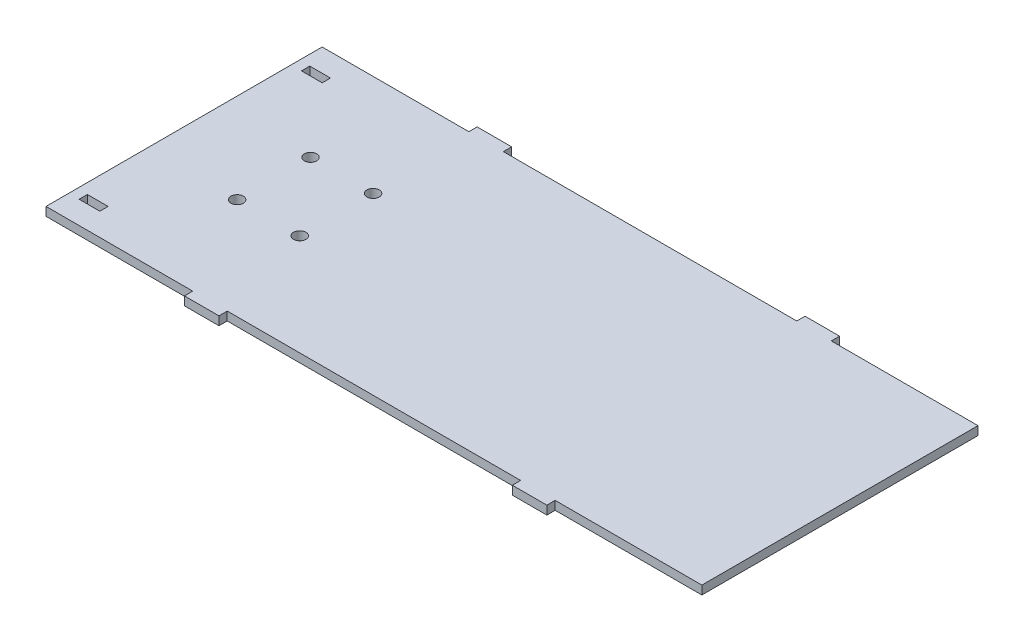
SolidWorks part; units mm, degrees
ref_plane "Front Plane" through (0, 0, 0) normal (0, 0, 1) x (1, 0, 0)
ref_plane "Top Plane" through (0, 0, 0) normal (0, 1, 0) x (1, 0, 0)
ref_plane "Right Plane" through (0, 0, 0) normal (1, 0, 0) x (0, 0, -1)
sketch "Sketch1" plane through (0, 0, 0) normal (0, 1, 0) x (1, 0, 0)
  line L0 (-12.7, 76.2164) -> (228.6, 76.2164) construction
  line L1 (0, 0) -> (41.275, 0)
  line L3 (0, 101.6) -> (41.275, 101.6)
  line L4 (228.6, 0) -> (228.6, 101.6)
  line L9 (0, 0) -> (-12.7, 0)
  line L11 (0, 101.6) -> (-12.7, 101.6)
  line L12 (-12.7, 0) -> (-12.7, 101.6)
  line L13 (107.95, 50.8) -> (228.6, 50.8) construction
  line L14 (174.625, 101.6) -> (228.6, 101.6)
  line L16 (161.925, 101.6) -> (161.925, 104.648)
  line L17 (161.925, 104.648) -> (174.625, 104.648)
  line L18 (174.625, 101.6) -> (174.625, 104.648)
  line L19 (107.95, 76.2164) -> (107.95, 0) construction
  line L20 (174.625, 0) -> (174.625, -3.048)
  line L21 (161.925, 0) -> (161.925, -3.048)
  line L22 (161.925, -3.048) -> (174.625, -3.048)
  line L23 (41.275, 0) -> (41.275, -3.048)
  line L24 (53.975, 0) -> (53.975, -3.048)
  line L25 (53.975, -3.048) -> (41.275, -3.048)
  line L26 (41.275, 101.6) -> (41.275, 104.648)
  line L27 (53.975, 101.6) -> (53.975, 104.648)
  line L28 (53.975, 104.648) -> (41.275, 104.648)
  line L29 (174.625, 0) -> (228.6, 0)
  line L30 (53.975, 101.6) -> (161.925, 101.6)
  line L31 (53.975, 0) -> (161.925, 0)
  point P15 (168.275, 104.648)
  point P16 (168.275, 50.8)
  dimension "D1" = 228.6
  dimension "D2" = 101.6
  dimension "D3" = 3.048
  dimension "D4" = 12.7
extrude "Main Frame" add sketch "Sketch1" along normal blind 3.175
sketch "Sketch2" plane through (0, 3.175, 0) normal (0, 1, 0) x (1, 0, 0)
  line L0 (0, 50.8) -> (228.6, 50.8) construction
  line L1 (-12.7, 101.6) -> (-12.7, 0) construction
  line L2 (228.6, 0) -> (228.6, 101.6) construction
  line L3 (25.1837, 69.85) -> (25.1837, 31.75) construction
  line L4 (8.6737, 69.85) -> (41.6937, 69.85) construction
  line L5 (8.6737, 69.85) -> (8.6737, 31.75) construction
  line L6 (8.6737, 31.75) -> (41.6937, 31.75) construction
  line L7 (41.6937, 69.85) -> (41.6937, 31.75) construction
  line L8 (0, 101.6) -> (0, 0) construction
  line L9 (41.275, 101.6) -> (-12.7, 101.6) construction
  circle A0 centre (20.32, 64.2938) radius 2.277
  circle A1 centre (43.3388, 64.2938) radius 2.277
  circle A2 centre (43.3388, 37.3062) radius 2.277
  circle A3 centre (20.32, 37.3062) radius 2.277
  point P10 (8.6737, 50.8)
  dimension "D1" = 33.02
  dimension "D2" = 38.1
  dimension "D3" = 13.4937
  dimension "D4" = 23.0188
  dimension "D5" = 33.02
extrude "Front Wheel" cut sketch "Sketch2" against normal through all
sketch "Sketch4" plane through (0, 3.175, 0) normal (0, 1, 0) x (1, 0, 0)
  line L0 (-12.7, 50.8) -> (228.6, 50.8) construction
  line L1 (-8.89, 93.2319) -> (-1.27, 93.2319)
  line L2 (-8.89, 93.2319) -> (-8.89, 90.1839)
  line L3 (-8.89, 90.1839) -> (-1.27, 90.1839)
  line L4 (-1.27, 93.2319) -> (-1.27, 90.1839)
  line L5 (-12.7, 101.6) -> (-12.7, 0) construction
  line L6 (228.6, 0) -> (228.6, 101.6) construction
  line L7 (-8.89, 8.3681) -> (-8.89, 11.4161)
  line L8 (-1.27, 8.3681) -> (-1.27, 11.4161)
  line L9 (-8.89, 11.4161) -> (-1.27, 11.4161)
  line L10 (-8.89, 8.3681) -> (-1.27, 8.3681)
  line L11 (41.275, 101.6) -> (-12.7, 101.6) construction
  dimension "D1" = 7.62
  dimension "D2" = 3.048
  dimension "D3" = 3.81
  dimension "D4" = 8.3681
extrude "Sensor Holes" cut sketch "Sketch4" against normal through all
